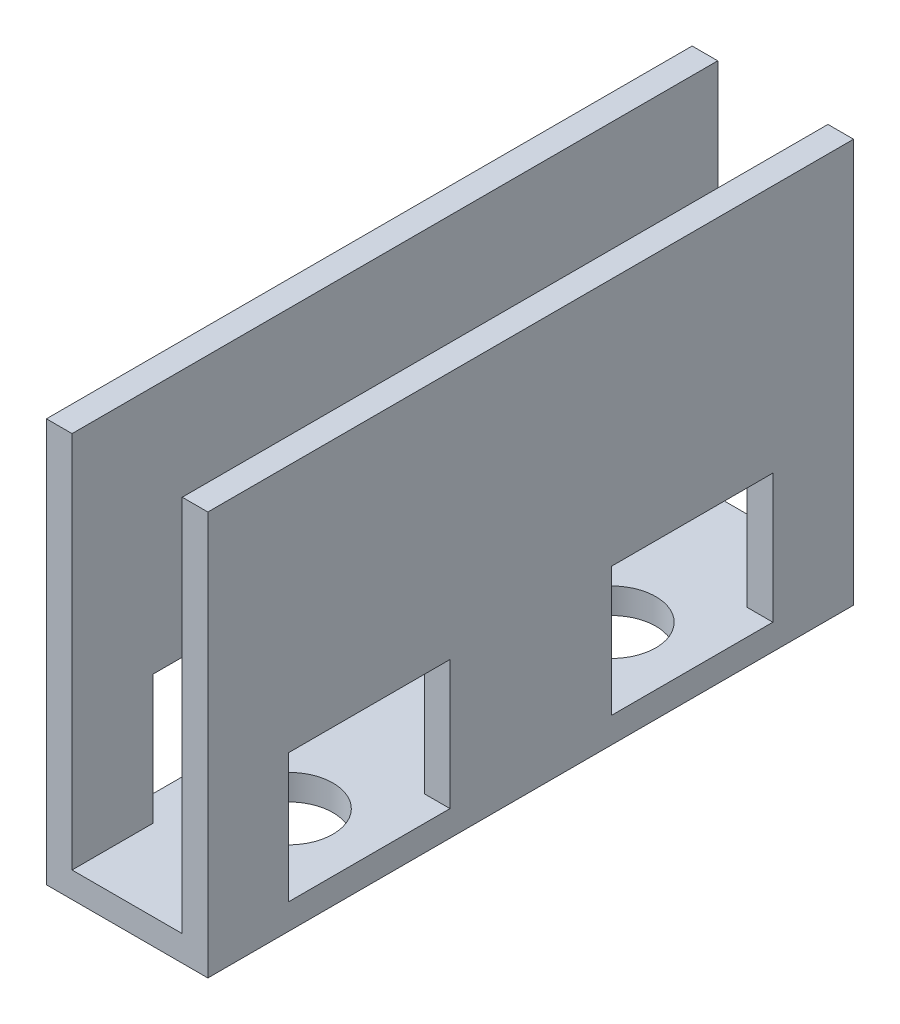
SolidWorks part; units mm, degrees
ref_plane "Front Plane" through (0, 0, 0) normal (0, 0, 1) x (1, 0, 0)
ref_plane "Top Plane" through (0, 0, 0) normal (0, 1, 0) x (1, 0, 0)
ref_plane "Right Plane" through (0, 0, 0) normal (1, 0, 0) x (0, 0, -1)
sketch "Sketch1" plane through (0, 0, 0) normal (0, 1, 0) x (1, 0, 0)
  line L0 (0, -10) -> (0, 10)
  line L1 (-5, -20) -> (5, -20)
  line L2 (-5, -20) -> (-5, 20)
  line L3 (-5, 20) -> (5, 20)
  line L4 (5, -20) -> (5, 20)
  line L5 (-5, -20) -> (5, 20) construction
  line L6 (-5, 20) -> (5, -20) construction
  line L7 (-3.4125, -20) -> (3.4125, -20)
  line L8 (-3.4125, -20) -> (-3.4125, 20)
  line L9 (-3.4125, 20) -> (3.4125, 20)
  line L10 (3.4125, -20) -> (3.4125, 20)
  line L11 (-3.4125, -20) -> (3.4125, 20) construction
  line L12 (-3.4125, 20) -> (3.4125, -20) construction
  circle A1 centre (0, 10) radius 2.75
  circle A2 centre (0, -10) radius 2.75
  point P0 (0, 0)
  point P13 (0, 0)
  dimension "D3" = 5.5
  dimension "D1" = 40
  dimension "D2" = 10
  dimension "D4" = 1.5875
  dimension "D5" = 20
extrude "Boss-Extrude1" add sketch "Sketch1" along normal blind 1.5875 contours L2 L8 L3 | L8 L10 L3 | L10 L4 L3 | L10 L4 | L8 L10 | L2 L8 | L2 L1 L8 | L8 L1 L10 | L10 L1 L4 region at (-4.2062, 0, 0) region at (-3.0067, 0, 0) region at (4.2063, 0, 0)
extrude "Boss-Extrude2" add sketch "Sketch1<3>" along normal blind 25 contours L1 L8 L3 L2 | L10 L1 L4 L3 region at (-4.2062, 0, 0) region at (4.2063, 0, 0)
sketch "Sketch1<3>" plane through (0, 0, 0) normal (0, 1, 0) x (1, 0, 0) same geometry as "Sketch1"
sketch "Sketch2" plane through (5, 0, 0) normal (1, 0, 0) x (0, 0, -1)
  line L0 (20, 1.5875) -> (-20, 1.5875) construction
  line L1 (20, 1.5875) -> (-20, 1.5875) construction
  line L2 (-15, 9.5875) -> (-20, 9.5875) construction
  line L3 (-15, 1.5875) -> (-5, 1.5875)
  line L4 (-15, 1.5875) -> (-15, 9.5875)
  line L5 (-15, 9.5875) -> (-5, 9.5875)
  line L6 (-5, 1.5875) -> (-5, 9.5875)
  line L7 (15, 1.5875) -> (5, 1.5875)
  line L8 (15, 1.5875) -> (15, 9.5875)
  line L9 (15, 9.5875) -> (5, 9.5875)
  line L10 (5, 1.5875) -> (5, 9.5875)
  line L11 (-20, 25) -> (-20, 0) construction
  line L12 (15, 9.5875) -> (20, 9.5875) construction
  line L13 (20, 25) -> (20, 0) construction
  point P10 (10, 9.5875)
  dimension "D1" = 10
  dimension "D2" = 10
  dimension "D3" = 8
extrude "Cut-Extrude1" cut sketch "Sketch2" against normal through all
